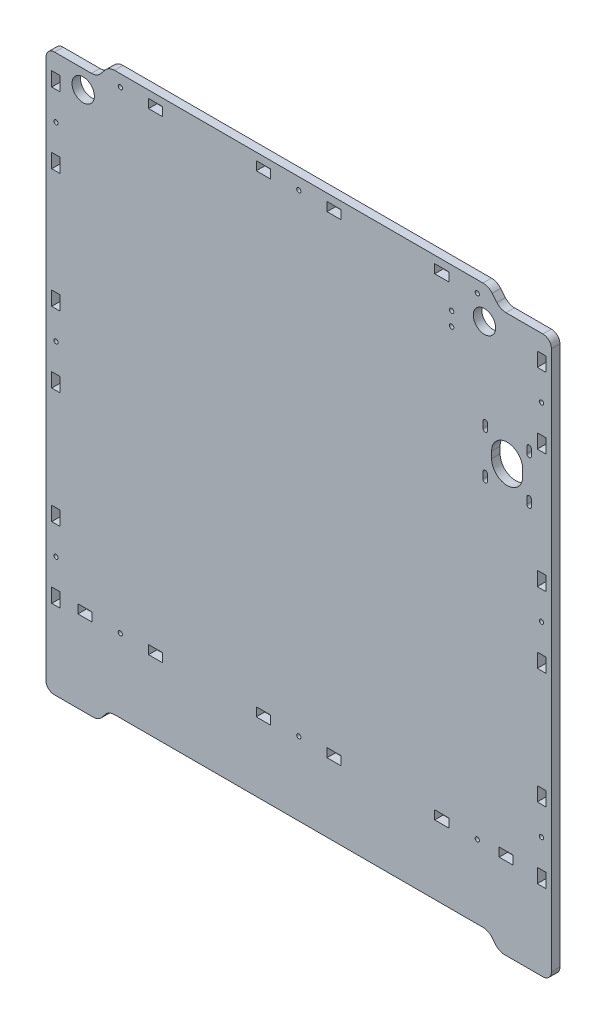
SolidWorks part; units mm, degrees
ref_plane "Спереди" through (0, 0, 0) normal (0, 0, 1) x (1, 0, 0)
ref_plane "Сверху" through (0, 0, 0) normal (0, 1, 0) x (1, 0, 0)
ref_plane "Справа" through (0, 0, 0) normal (1, 0, 0) x (0, 0, -1)
sketch "Эскиз1" plane through (0, 0, 0) normal (0, 0, 1) x (1, 0, 0)
  line L0 (133.6555, 83.4698) -> (133.6555, 87.9698)
  line L1 (133.6555, 118.9698) -> (133.6555, 114.4698)
  line L2 (130.4555, 83.4698) -> (130.4555, 87.9698)
  line L3 (158.5555, 98.9698) -> (158.5555, 103.4698)
  line L4 (130.4555, 118.9698) -> (130.4555, 114.4698)
  line L5 (161.4555, 118.9698) -> (161.4555, 114.4698)
  line L6 (164.6555, 118.9698) -> (164.6555, 114.4698)
  line L7 (136.5555, 98.9698) -> (136.5555, 103.4698)
  line L8 (161.4555, 83.4698) -> (161.4555, 87.9698)
  line L9 (164.6555, 83.4698) -> (164.6555, 87.9698)
  line L10 (-174.1809, 36.7423) -> (-174.1809, 46.7423)
  line L11 (106.3726, -142.2004) -> (96.3778, -142.2004)
  line L12 (96.3778, -142.2004) -> (96.3778, -136.0006)
  line L13 (96.3778, -136.0006) -> (106.3726, -136.0006)
  line L14 (106.3726, -136.0006) -> (106.3726, -142.2004)
  line L15 (151.7592, -142.2004) -> (141.91, -142.2004)
  line L16 (141.91, -142.2004) -> (141.91, -136.0006)
  line L17 (141.91, -136.0006) -> (151.7592, -136.0006)
  line L18 (151.7592, -136.0006) -> (151.7592, -142.2004)
  line L19 (-19.7199, 191.9054) -> (-29.6916, 191.9054)
  line L20 (-29.6916, 191.9054) -> (-29.6916, 198.1051)
  line L21 (-29.6916, 198.1051) -> (-19.7199, 198.1051)
  line L22 (-19.7199, 198.1051) -> (-19.7199, 191.9054)
  line L23 (30.2801, 191.9054) -> (20.3037, 191.9054)
  line L24 (20.3037, 191.9054) -> (20.3037, 198.1051)
  line L25 (20.3037, 198.1051) -> (30.2801, 198.1051)
  line L26 (30.2801, 198.1051) -> (30.2801, 191.9054)
  line L27 (-145.8164, -142.2004) -> (-155.6656, -142.2004)
  line L28 (-155.6656, -142.2004) -> (-155.6656, -136.0006)
  line L29 (-155.6656, -136.0006) -> (-145.8164, -136.0006)
  line L30 (-145.8164, -136.0006) -> (-145.8164, -142.2004)
  line L31 (-95.8164, -142.2004) -> (-105.7664, -142.2004)
  line L32 (-105.7664, -142.2004) -> (-105.7664, -136.0006)
  line L33 (-105.7664, -136.0006) -> (-95.8164, -136.0006)
  line L34 (-95.8164, -136.0006) -> (-95.8164, -142.2004)
  line L35 (-19.722, -142.199) -> (-29.6916, -142.199)
  line L36 (-29.6916, -142.199) -> (-29.6916, -135.9992)
  line L37 (-29.6916, -135.9992) -> (-19.722, -135.9992)
  line L38 (-19.722, -135.9992) -> (-19.722, -142.199)
  line L39 (30.2781, -142.199) -> (20.3037, -142.199)
  line L40 (20.3037, -142.199) -> (20.3037, -135.9992)
  line L41 (20.3037, -135.9992) -> (30.2781, -135.9992)
  line L42 (30.2781, -135.9992) -> (30.2781, -142.199)
  line L43 (-174.1809, 46.7423) -> (-168.1809, 46.7423)
  line L44 (-168.1809, 46.7423) -> (-168.1809, 36.7423)
  line L45 (-168.1809, 36.7423) -> (-174.1809, 36.7423)
  line L46 (-174.1809, -13.2577) -> (-174.1809, -3.2577)
  line L47 (-174.1809, -3.2577) -> (-168.1809, -3.2577)
  line L48 (-168.1809, -3.2577) -> (-168.1809, -13.2577)
  line L49 (-168.1809, -13.2577) -> (-174.1809, -13.2577)
  line L50 (-174.1809, 170.9023) -> (-174.1809, 180.9023)
  line L51 (-174.1809, 180.9023) -> (-168.1809, 180.9023)
  line L52 (-168.1809, 180.9023) -> (-168.1809, 170.9023)
  line L53 (-168.1809, 170.9023) -> (-174.1809, 170.9023)
  line L54 (-174.1809, 120.9023) -> (-174.1809, 130.9023)
  line L55 (-174.1809, 130.9023) -> (-168.1809, 130.9023)
  line L56 (-168.1809, 130.9023) -> (-168.1809, 120.9023)
  line L57 (-168.1809, 120.9023) -> (-174.1809, 120.9023)
  line L58 (-174.1809, -94.9877) -> (-174.1809, -84.9877)
  line L59 (-174.1809, -84.9877) -> (-168.1809, -84.9877)
  line L62 (-174.1809, -144.9777) -> (-174.1809, -134.9777)
  line L63 (-174.1809, -134.9777) -> (-168.1809, -134.9777)
  line L64 (-168.1809, -134.9777) -> (-168.1809, -144.9777)
  line L65 (-168.1809, -144.9777) -> (-174.1809, -144.9777)
  line L66 (168.8191, 36.7421) -> (168.8191, 46.7421)
  line L67 (168.8191, 46.7421) -> (174.8191, 46.7421)
  line L68 (174.8191, 46.7421) -> (174.8191, 36.7421)
  line L69 (174.8191, 36.7421) -> (168.8191, 36.7421)
  line L70 (168.8191, -13.2579) -> (168.8191, -3.2579)
  line L71 (168.8191, -3.2579) -> (174.8191, -3.2579)
  line L72 (174.8191, -3.2579) -> (174.8191, -13.2579)
  line L73 (174.8191, -13.2579) -> (168.8191, -13.2579)
  line L74 (168.8191, -94.9879) -> (168.8191, -84.9879)
  line L75 (168.8191, -84.9879) -> (174.8191, -84.9879)
  line L76 (174.8191, -84.9879) -> (174.8191, -94.9879)
  line L77 (174.8191, -94.9879) -> (168.8191, -94.9879)
  line L78 (168.8191, -144.9779) -> (168.8191, -134.9779)
  line L79 (168.8191, -134.9779) -> (174.8191, -134.9779)
  line L80 (174.8191, -134.9779) -> (174.8191, -144.9779)
  line L81 (174.8191, -144.9779) -> (168.8191, -144.9779)
  line L82 (168.8191, 170.9021) -> (168.8191, 180.9021)
  line L83 (168.8191, 180.9021) -> (174.8191, 180.9021)
  line L84 (175.1997, 170.9021) -> (168.8191, 170.9021)
  line L85 (168.8191, 120.9021) -> (168.8191, 130.9021)
  line L86 (168.8191, 130.9021) -> (174.8191, 130.9021)
  line L87 (174.8191, 130.9021) -> (174.8191, 120.9021)
  line L88 (174.8191, 120.9021) -> (168.8191, 120.9021)
  line L89 (-105.7664, 198.1027) -> (-95.7933, 198.1027)
  line L90 (-95.7933, 198.1027) -> (-95.7933, 191.903)
  line L91 (-95.7933, 191.903) -> (-105.7664, 191.903)
  line L92 (-105.7664, 191.903) -> (-105.7664, 198.1027)
  line L93 (106.3778, 191.903) -> (106.177, 191.9198)
  line L94 (96.3778, 191.903) -> (96.3778, 198.1027)
  line L95 (106.3778, 198.1027) -> (106.3778, 191.903)
  line L96 (146.7829, 193.3021) -> (172.8193, 193.3021)
  line L97 (106.177, 191.9198) -> (96.3778, 191.903)
  line L99 (-136.3371, 200.266) -> (-139.6329, 196.3386)
  line L100 (130.4644, 203.3023) -> (-129.8257, 203.3023)
  line L101 (136.9757, 200.266) -> (140.2716, 196.3385)
  line L102 (174.8191, 170.9781) -> (175.1997, 170.9021)
  line L103 (106.177, 198.1198) -> (106.3778, 198.1027)
  line L104 (96.3778, 198.1027) -> (106.177, 198.1198)
  line L105 (174.8191, 180.9021) -> (174.8191, 170.9781)
  line L106 (139.2716, -196.9614) -> (136.9757, -193.9418)
  line L107 (-129.8257, -190.9055) -> (130.4644, -190.9055)
  line L108 (-172.1807, -199.9977) -> (-145.1443, -199.9977)
  line L109 (-138.6329, -196.9614) -> (-136.3371, -193.9418)
  line L110 (172.8193, -199.9977) -> (145.7829, -199.9977)
  line L111 (-178.1809, 187.3023) -> (-178.1809, -195.6332)
  line L112 (178.8191, 187.3133) -> (178.8191, -193.9977)
  line L113 (-174.1809, -94.9877) -> (-168.1809, -94.9877)
  line L114 (-168.1809, -94.9877) -> (-168.1809, -84.9877)
  line L115 (-172.1809, 193.3023) -> (-146.1443, 193.3023)
  arc A0 (158.5555, 103.4698) -> (136.5555, 103.4698) centre (147.5555, 103.4698) ccw
  arc A1 (161.4555, 83.4698) -> (164.6555, 83.4698) centre (163.0555, 83.4698) ccw
  arc A2 (136.5555, 98.9698) -> (158.5555, 98.9698) centre (147.5555, 98.9698) ccw
  arc A3 (130.4555, 83.4698) -> (133.6555, 83.4698) centre (132.0555, 83.4698) ccw
  arc A4 (164.6555, 87.9698) -> (161.4555, 87.9698) centre (163.0555, 87.9698) ccw
  circle A5 centre (108.3191, 165.6023) radius 1.55
  circle A6 centre (108.3191, 175.3023) radius 1.55
  arc A7 (130.4555, 114.4698) -> (133.6555, 114.4698) centre (132.0555, 114.4698) ccw
  arc A8 (133.6555, 118.9698) -> (130.4555, 118.9698) centre (132.0555, 118.9698) ccw
  arc A9 (164.6555, 118.9698) -> (161.4555, 118.9698) centre (163.0555, 118.9698) ccw
  arc A10 (161.4555, 114.4698) -> (164.6555, 114.4698) centre (163.0555, 114.4698) ccw
  arc A11 (133.6555, 87.9698) -> (130.4555, 87.9698) centre (132.0555, 87.9698) ccw
  circle A12 centre (131.5191, 180.3023) radius 7.9
  circle A13 centre (-151.9809, 180.3023) radius 7.9
  arc A14 (-129.8257, 203.3023) -> (-136.3371, 200.266) centre (-129.8257, 194.8023) ccw
  arc A15 (-146.1443, 193.3023) -> (-139.6329, 196.3386) centre (-146.1443, 201.8023) ccw
  arc A17 (140.2716, 196.3385) -> (146.7829, 193.3021) centre (146.7831, 201.8021) ccw
  arc A18 (136.9757, 200.266) -> (130.4644, 203.3023) centre (130.4644, 194.8023) ccw
  arc A19 (178.8191, 187.3133) -> (172.8193, 193.3021) centre (172.8191, 187.3021) ccw
  arc A20 (136.9757, -193.9418) -> (130.4644, -190.9055) centre (130.4644, -199.4055) ccw
  arc A21 (-178.1809, -195.6332) -> (-172.1807, -199.9977) centre (-172.4069, -194.002) ccw
  arc A22 (-145.1443, -199.9977) -> (-138.6329, -196.9614) centre (-145.1443, -191.4977) ccw
  arc A23 (139.2716, -196.9614) -> (145.7829, -199.9977) centre (145.7829, -191.4977) ccw
  arc A24 (-129.8257, -190.9055) -> (-136.3371, -193.9418) centre (-129.8257, -199.4055) ccw
  circle A25 centre (-171.1809, 150.9023) radius 1.5
  arc A26 (172.8193, -199.9977) -> (178.8191, -193.9977) centre (172.8191, -193.9977) ccw
  circle A27 centre (-171.1809, 16.7423) radius 1.5
  circle A28 centre (171.8191, 150.9021) radius 1.5
  circle A29 centre (126.4621, 195.0571) radius 1.5
  circle A30 centre (-125.7107, 195.0571) radius 1.5
  circle A31 centre (0.3581, 195.0571) radius 1.5
  circle A32 centre (-125.7495, -139.0659) radius 1.5
  circle A33 centre (-171.1809, -114.9677) radius 1.5
  circle A34 centre (0.3757, -139.0659) radius 1.5
  circle A35 centre (126.4428, -139.0659) radius 1.5
  circle A36 centre (171.8191, -114.9679) radius 1.5
  circle A37 centre (171.8191, 16.7421) radius 1.5
  arc A38 (-178.1809, 187.3023) -> (-172.1809, 193.3023) centre (-172.1809, 187.3023) cw
  point P149 (159.3011, -199.9977)
  point P191 (171.8191, -13.2579)
  point P192 (174.8191, -89.9879)
  dimension "D9" = 15.8
  dimension "D24" = 8.5
  dimension "D25" = 8.5
  dimension "D26" = 6
  dimension "D27" = 8.5
  dimension "D28" = 8.5
  dimension "D29" = 4
  dimension "D30" = 6
  dimension "D32" = 12.4
  dimension "D40" = 20
  dimension "D82" = 9.7
  dimension "D83" = 28
  dimension "D84" = 70.5
  dimension "D3" = 10
  dimension "D4" = 20
  dimension "D5" = 20
  dimension "D6" = 10
  dimension "D7" = 6
  dimension "D8" = 6
  dimension "D10" = 74.16
  dimension "D11" = 10
  dimension "D12" = 6
  dimension "D13" = 20
  dimension "D14" = 6
  dimension "D15" = 10
  dimension "D16" = 71.73
  dimension "D17" = 6
  dimension "D18" = 10
  dimension "D19" = 20.01
  dimension "D20" = 10
  dimension "D21" = 20
  dimension "D22" = 403.3
  dimension "D23" = 19.98
  dimension "D31" = 10
  dimension "D33" = 10
  dimension "D34" = 55.02
  dimension "D35" = 6
  dimension "D36" = 10.0002
  dimension "D37" = 12.4
  dimension "D38" = 10
  dimension "D39" = 20
  dimension "D41" = 6
  dimension "D42" = 6
  dimension "D43" = 74.16
  dimension "D44" = 10
  dimension "D45" = 6
  dimension "D46" = 20
  dimension "D47" = 20
  dimension "D48" = 6
  dimension "D49" = 10
  dimension "D50" = 71.73
  dimension "D51" = 6
  dimension "D52" = 10
  dimension "D53" = 19.98
  dimension "D54" = 10
  dimension "D55" = 6
  dimension "D56" = 20.01
  dimension "D57" = 403.3
  dimension "D58" = 283.5
  dimension "D59" = 55.0198
  dimension "D60" = 357
  dimension "D61" = 26.2
  dimension "D62" = 47.3
  dimension "D63" = 23
  dimension "D64" = 23
  dimension "D65" = 7
  dimension "D66" = 4
  dimension "D67" = 4
  dimension "D68" = 7
  dimension "D69" = 4
  dimension "D70" = 4
  dimension "D71" = 7
  dimension "D72" = 4
  dimension "D73" = 4
  dimension "D74" = 7
  dimension "D75" = 4
  dimension "D76" = 4
  dimension "D77" = 7
  dimension "D78" = 4
  dimension "D79" = 4
  dimension "D80" = 7
  dimension "D81" = 4
extrude "Бобышка-Вытянуть1" add sketch "Эскиз1" along normal blind 6
